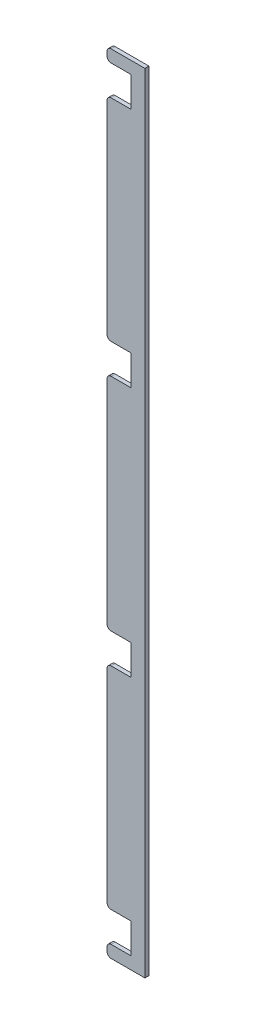
SolidWorks part; units mm, degrees
ref_plane "Front Plane" through (0, 0, 0) normal (0, 0, 1) x (1, 0, 0)
ref_plane "Top Plane" through (0, 0, 0) normal (0, 1, 0) x (1, 0, 0)
ref_plane "Right Plane" through (0, 0, 0) normal (1, 0, 0) x (0, 0, -1)
sketch "Sketch1" plane through (0, 0, 0) normal (0, 0, 1) x (1, 0, 0)
  line L0 (0, -182.5952) -> (-4.5, -182.5952)
  line L2 (0, 13.4048) -> (0, -182.5952)
  line L6 (-4.5, 10.3548) -> (-3.5, 10.3548)
  line L7 (-3.5, 10.3548) -> (-3.5, 2.8548)
  line L9 (-3.5, 2.8548) -> (-4.5, 2.8548)
  line L10 (-4.5, -49.6452) -> (-3.5, -49.6452)
  line L11 (-3.5, -49.6452) -> (-3.5, -57.1452)
  line L12 (-3.5, -57.1452) -> (-4.5, -57.1452)
  line L13 (-4.5, -112.0452) -> (-3.5, -112.0452)
  line L14 (-3.5, -112.0452) -> (-3.5, -119.5452)
  line L15 (-3.5, -119.5452) -> (-4.5, -119.5452)
  line L16 (-4.5, -172.0452) -> (-3.5, -172.0452)
  line L17 (-3.5, -172.0452) -> (-3.5, -179.5452)
  line L18 (-3.5, -179.5452) -> (-4.5, -179.5452)
  line L87 (0, -74.1952) -> (0, -94.9952) construction
  line L100 (-8.4, 10.3548) -> (-4.5, 10.3548)
  line L101 (-4.5, 10.3548) -> (-4.5, 2.8548)
  line L102 (-4.5, 2.8548) -> (-8.4, 2.8548)
  line L103 (-9.4, 1.8548) -> (-9.4, -48.6452)
  line L104 (-8.4, -49.6452) -> (-4.5, -49.6452)
  line L105 (-4.5, -49.6452) -> (-4.5, -57.1452)
  line L106 (-4.5, -57.1452) -> (-8.4, -57.1452)
  line L107 (-9.4, -58.1452) -> (-9.4, -111.0452)
  line L108 (-8.4, -112.0452) -> (-4.5, -112.0452)
  line L109 (-4.5, -112.0452) -> (-4.5, -119.5452)
  line L110 (-4.5, -119.5452) -> (-8.4, -119.5452)
  line L111 (-9.4, -120.5452) -> (-9.4, -171.0452)
  line L112 (-8.4, -172.0452) -> (-4.5, -172.0452)
  line L113 (-4.5, -172.0452) -> (-4.5, -179.5452)
  line L114 (-4.5, -179.5452) -> (-8.4, -179.5452)
  line L115 (-9.4, -180.5452) -> (-9.4, -181.5952)
  line L116 (-8.4, -182.5952) -> (-4.5, -182.5952)
  line L117 (-4.5, -182.5952) -> (-4.5, -191.5952)
  line L118 (-4.5, -191.5952) -> (78.5, -191.5952)
  line L119 (78.5, -191.5952) -> (78.5, -182.5952)
  line L120 (78.5, -182.5952) -> (82.4, -182.5952)
  line L121 (83.4, -181.5952) -> (83.4, -180.5452)
  line L122 (82.4, -179.5452) -> (78.5, -179.5452)
  line L123 (78.5, -179.5452) -> (78.5, -172.0452)
  line L124 (78.5, -172.0452) -> (82.4, -172.0452)
  line L125 (83.4, -171.0452) -> (83.4, -120.5452)
  line L126 (82.4, -119.5452) -> (78.5, -119.5452)
  line L127 (78.5, -119.5452) -> (78.5, -112.0452)
  line L128 (78.5, -112.0452) -> (82.4, -112.0452)
  line L129 (83.4, -111.0452) -> (83.4, -58.1452)
  line L130 (82.4, -57.1452) -> (78.5, -57.1452)
  line L131 (78.5, -57.1452) -> (78.5, -49.6452)
  line L132 (78.5, -49.6452) -> (82.4, -49.6452)
  line L133 (83.4, -48.6452) -> (83.4, 1.8548)
  line L134 (82.4, 2.8548) -> (78.5, 2.8548)
  line L135 (78.5, 2.8548) -> (78.5, 10.3548)
  line L136 (78.5, 10.3548) -> (82.4, 10.3548)
  line L137 (83.4, 11.3548) -> (83.4, 12.4048)
  line L138 (82.4, 13.4048) -> (78.5, 13.4048)
  line L139 (78.5, 13.4048) -> (78.5, 22.4048)
  line L140 (78.5, 22.4048) -> (-4.5, 22.4048)
  line L141 (-4.5, 22.4048) -> (-4.5, 13.4048)
  line L142 (-4.5, 13.4048) -> (-8.4, 13.4048)
  line L143 (-9.4, 12.4048) -> (-9.4, 11.3548)
  line L144 (-8.4, 10.3548) -> (-4.5, 10.3548)
  line L145 (-4.5, 10.3548) -> (-4.5, 2.8548)
  line L146 (-4.5, 2.8548) -> (-8.4, 2.8548)
  line L147 (-9.4, 1.8548) -> (-9.4, -48.6452)
  line L148 (-8.4, -49.6452) -> (-4.5, -49.6452)
  line L149 (-4.5, -49.6452) -> (-4.5, -57.1452)
  line L150 (-4.5, -57.1452) -> (-8.4, -57.1452)
  line L151 (-9.4, -58.1452) -> (-9.4, -111.0452)
  line L152 (-8.4, -112.0452) -> (-4.5, -112.0452)
  line L153 (-4.5, -112.0452) -> (-4.5, -119.5452)
  line L154 (-4.5, -119.5452) -> (-8.4, -119.5452)
  line L155 (-9.4, -120.5452) -> (-9.4, -171.0452)
  line L156 (-8.4, -172.0452) -> (-4.5, -172.0452)
  line L157 (-4.5, -172.0452) -> (-4.5, -179.5452)
  line L158 (-4.5, -179.5452) -> (-8.4, -179.5452)
  line L159 (-9.4, -180.5452) -> (-9.4, -181.5952)
  line L160 (-8.4, -182.5952) -> (-4.5, -182.5952)
  line L186 (0, 13.4048) -> (-8.4, 13.4048)
  line L187 (-9.4, 12.4048) -> (-9.4, 11.3548)
  arc A40 (-8.4, 2.8548) -> (-9.4, 1.8548) centre (-8.4, 1.8548) ccw
  arc A41 (-9.4, -48.6452) -> (-8.4, -49.6452) centre (-8.4, -48.6452) ccw
  arc A42 (-8.4, -57.1452) -> (-9.4, -58.1452) centre (-8.4, -58.1452) ccw
  arc A43 (-9.4, -111.0452) -> (-8.4, -112.0452) centre (-8.4, -111.0452) ccw
  arc A44 (-8.4, -119.5452) -> (-9.4, -120.5452) centre (-8.4, -120.5452) ccw
  arc A45 (-9.4, -171.0452) -> (-8.4, -172.0452) centre (-8.4, -171.0452) ccw
  arc A46 (-8.4, -179.5452) -> (-9.4, -180.5452) centre (-8.4, -180.5452) ccw
  arc A47 (-9.4, -181.5952) -> (-8.4, -182.5952) centre (-8.4, -181.5952) ccw
  arc A48 (82.4, -182.5952) -> (83.4, -181.5952) centre (82.4, -181.5952) ccw
  arc A49 (83.4, -180.5452) -> (82.4, -179.5452) centre (82.4, -180.5452) ccw
  arc A50 (82.4, -172.0452) -> (83.4, -171.0452) centre (82.4, -171.0452) ccw
  arc A51 (83.4, -120.5452) -> (82.4, -119.5452) centre (82.4, -120.5452) ccw
  arc A52 (82.4, -112.0452) -> (83.4, -111.0452) centre (82.4, -111.0452) ccw
  arc A53 (83.4, -58.1452) -> (82.4, -57.1452) centre (82.4, -58.1452) ccw
  arc A54 (82.4, -49.6452) -> (83.4, -48.6452) centre (82.4, -48.6452) ccw
  arc A55 (83.4, 1.8548) -> (82.4, 2.8548) centre (82.4, 1.8548) ccw
  arc A56 (82.4, 10.3548) -> (83.4, 11.3548) centre (82.4, 11.3548) ccw
  arc A57 (83.4, 12.4048) -> (82.4, 13.4048) centre (82.4, 12.4048) ccw
  arc A58 (-8.4, 13.4048) -> (-9.4, 12.4048) centre (-8.4, 12.4048) ccw
  arc A59 (-9.4, 11.3548) -> (-8.4, 10.3548) centre (-8.4, 11.3548) ccw
  arc A60 (-8.4, 2.8548) -> (-9.4, 1.8548) centre (-8.4, 1.8548) ccw
  arc A61 (-9.4, -48.6452) -> (-8.4, -49.6452) centre (-8.4, -48.6452) ccw
  arc A62 (-8.4, -57.1452) -> (-9.4, -58.1452) centre (-8.4, -58.1452) ccw
  arc A63 (-9.4, -111.0452) -> (-8.4, -112.0452) centre (-8.4, -111.0452) ccw
  arc A64 (-8.4, -119.5452) -> (-9.4, -120.5452) centre (-8.4, -120.5452) ccw
  arc A65 (-9.4, -171.0452) -> (-8.4, -172.0452) centre (-8.4, -171.0452) ccw
  arc A66 (-8.4, -179.5452) -> (-9.4, -180.5452) centre (-8.4, -180.5452) ccw
  arc A67 (-9.4, -181.5952) -> (-8.4, -182.5952) centre (-8.4, -181.5952) ccw
  arc A78 (-8.4, 13.4048) -> (-9.4, 12.4048) centre (-8.4, 12.4048) ccw
  arc A79 (-9.4, 11.3548) -> (-8.4, 10.3548) centre (-8.4, 11.3548) ccw
  dimension "D1" = 1
  dimension "D2" = 0
extrude "Boss-Extrude1" add sketch "Sketch1" along normal blind 1 contours L2 region at (-4.508, -84.5952, 0)
